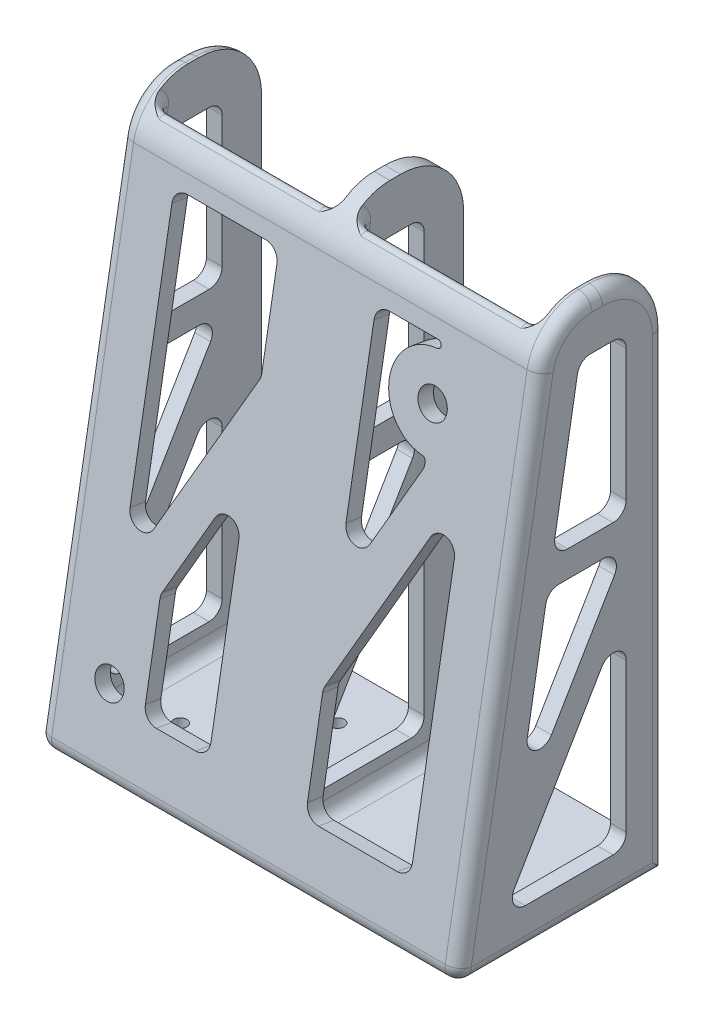
SolidWorks part; units mm, degrees
material "ABS"
ref_plane "X-Y Datum" through (0, 0, 0) normal (0, 0, 1) x (1, 0, 0)
ref_plane "X-Z Datum" through (0, 0, 0) normal (0, 1, 0) x (1, 0, 0)
ref_plane "Y-Z Datum" through (0, 0, 0) normal (1, 0, 0) x (0, 0, -1)
sketch "Sketch1" plane through (0, 0, 0) normal (1, 0, 0) x (0, 0, -1)
  line L0 (0, 0) -> (-50.8, 0)
  line L1 (-50.8, 0) -> (0, 294.1006)
  line L2 (0, 294.1006) -> (0, 0)
  dimension "D1" = 50.8
  dimension "D2" = 80.2
extrude "Boss-Extrude1" add sketch "Sketch1" along normal blind 101.6
fillet "Fillet1" [suppressed] radius 15.24
ref_plane "Plane2" through (50.8, 0, 0) normal (1, 0, 0) x (0, 0, -1)
sketch "Sketch3" plane through (50.8, 0, 0) normal (1, 0, 0) x (0, 0, -1)
  line L0 (-46.2755, 3.81) -> (-19.9514, 156.21)
  line L1 (-19.9514, 156.21) -> (0, 156.21)
  line L2 (0, 156.21) -> (0, 3.81)
  line L3 (0, 0) -> (0, 294.1006) construction
  line L4 (0, 3.81) -> (-46.2755, 3.81)
  line L5 (0, 294.1006) -> (-50.8, 0) construction
  line L6 (-46.2755, 3.81) -> (-46.2755, 0) construction
  line L7 (-50.8, 0) -> (0, 0) construction
  line L8 (-46.2755, 3.81) -> (-50.0299, 4.4585) construction
  dimension "D1" = 3.81
  dimension "D2" = 152.4
extrude "Cut-Extrude1" cut sketch "Sketch3" against normal offset from surface (45.085 mm away) 3.81 from offset 1.905 up to face at (0, 98.0335, 16.9333) offset against normal yes
extrude "Cut-Extrude2" cut sketch "Sketch3<3>" along normal offset from surface (45.085 mm away) 3.81 from offset 1.905 up to face at (101.6, 98.0335, 16.9333)
sketch "Sketch3<3>" plane through (50.8, 0, 0) normal (1, 0, 0) x (0, 0, -1) same geometry as "Sketch3"
sketch "Sketch4" plane through (101.6, 0, 0) normal (1, 0, 0) x (0, 0, -1)
  line L0 (0, 294.1006) -> (-28.5177, 129.0006)
  line L1 (0, 294.1006) -> (-50.8, 0) construction
  line L2 (-28.5177, 129.0006) -> (0, 129.0006)
  line L3 (0, 0) -> (0, 294.1006) construction
  line L4 (0, 129.0006) -> (0, 294.1006)
  dimension "D1" = 165.1
extrude "Cut-Extrude3" cut sketch "Sketch4" against normal through all both and the other way through all
fillet "Fillet2" radius 15.24 3 edges at (99.695, 129.0006, 0) (50.8, 129.0006, 0) (1.905, 129.0006, 0)
fillet "Fillet3" radius 12.7 1 edges at (50.8, 129.0006, 28.5177)
fillet "Fillet4" radius 1.27 2 edges at (75.2475, 126.7511, 25.0399) (26.3525, 126.7511, 25.0399)
fillet "Fillet5" radius 3.175 27 edges at (97.79, 124.3552, 26.4387) (48.895, 124.3552, 26.4387) (52.705, 124.3552, 26.4387) (3.81, 124.3552, 26.4387) (52.705, 3.81, 23.1377) (3.81, 3.81, 23.1377) (48.895, 3.81, 23.1377) (97.79, 3.81, 23.1377) (97.79, 63.3919, 35.9839) (48.895, 63.3919, 35.9839) (52.705, 63.3919, 35.9839) (3.81, 63.3919, 35.9839) (75.2475, 3.81, 46.2755) (26.3525, 3.81, 46.2755) (101.6, 56.8803, 0) (101.6, 124.5369, 4.4637) (101.6, 126.0151, 26.0037) (0, 56.8803, 0) (0, 124.5369, 4.4637) (0, 126.0151, 26.0037) (101.6, 59.2311, 40.569) (0, 59.2311, 40.569) (0, 0, 25.4) (50.8, 0, 50.8) (101.6, 0, 25.4) (101.6, 129.0006, 16.5317) (0, 129.0006, 16.5317)
sketch "Sketch5" plane through (0, 8.5205, 49.3283) normal (0, 0.1702, 0.9854) x (1, 0, 0)
  circle A1 centre (78.2877, 95.5297) radius 3.5
  circle A2 centre (14.478, 10.922) radius 3.5
  point P4 (0, 0)
  dimension "D3" = 7
  dimension "D6" = 7
  dimension "D1" = 14.478
  dimension "D2" = 10.922
  dimension "D4" = 63.8097
  dimension "D5" = 84.6077
extrude "Cut-Extrude4" cut sketch "Sketch5" against normal up to next
sketch "Sketch6" plane through (0, 3.81, 0) normal (0, 1, 0) x (1, 0, 0)
  line L0 (94.615, 0) -> (55.88, 0) construction
  line L1 (66.675, -12.7) -> (34.925, -12.7) construction
  line L2 (50.8, -24.12) -> (50.8, 24.12) construction
  line L3 (85.725, -31.75) -> (15.875, -31.75) construction
  circle A0 centre (66.675, -12.7) radius 1.5875
  circle A1 centre (34.925, -12.7) radius 1.5875
  circle A2 centre (85.725, -31.75) radius 1.5875
  circle A3 centre (15.875, -31.75) radius 1.5875
  point P6 (50.8, -12.7)
  point P13 (50.8, -31.75)
  dimension "D3" = 3.175
  dimension "D1" = 12.7
  dimension "D2" = 31.75
  dimension "D4" = 69.85
  dimension "D5" = 19.05
extrude "Cut-Extrude5" cut sketch "Sketch6" against normal up to next
sketch "Sketch7" plane through (0, 7.872, 45.5739) normal (0, -0.1702, -0.9854) x (-1, 0, 0)
  line L0 (-62.5475, 6.9294) -> (-87.9475, 6.9294)
  line L1 (-87.9475, 6.9294) -> (-87.9475, 83.1294)
  line L3 (-101.6, 57.3469) -> (0, 57.3469) construction
  line L4 (-50.8, 124.5242) -> (-50.8, -3.4804) construction
  line L5 (-52.705, 124.5242) -> (-48.895, 124.5242) construction
  line L9 (-55.88, -3.4804) -> (-94.615, -3.4804) construction
  line L10 (-101.6, -4.8762) -> (-101.6, 2.5883) construction
  line L11 (0, 111.5602) -> (0, 121.5716) construction
  line L13 (-94.615, 3.7544) -> (-55.88, 3.7544) construction
  line L14 (-75.2475, 6.9294) -> (-75.2475, 3.7544) construction
  line L15 (-62.5475, 6.9294) -> (-62.5475, 32.3294)
  line L16 (-62.5475, 32.3294) -> (-87.9475, 83.1294)
  line L17 (-39.0525, 107.7645) -> (-39.0525, 82.3645)
  line L18 (-39.0525, 82.3645) -> (-13.6525, 31.5645)
  line L19 (-13.6525, 107.7645) -> (-13.6525, 31.5645)
  line L20 (-39.0525, 107.7645) -> (-13.6525, 107.7645)
  line L21 (-87.9475, 83.1294) -> (-50.8, 57.3469) construction
  line L22 (-50.8, 57.3469) -> (-13.6525, 31.5645) construction
  line L24 (-62.5475, 83.1294) -> (-62.5475, 51.3794)
  line L25 (-62.5475, 51.3794) -> (-78.4225, 83.1294)
  line L27 (-39.0525, 32.3294) -> (-39.0525, 64.0794)
  line L28 (-39.0525, 64.0794) -> (-23.1775, 32.3294)
  line L29 (-78.4225, 83.1294) -> (-78.4225, 107.7645)
  line L30 (-62.5475, 107.7645) -> (-62.5475, 83.1294)
  line L31 (-78.4225, 107.7645) -> (-62.5475, 107.7645)
  line L33 (-23.1775, 32.3294) -> (-23.1775, 7.6943)
  line L34 (-23.1775, 7.6943) -> (-39.0525, 7.6943)
  line L35 (-39.0525, 7.6943) -> (-39.0525, 32.3294)
  point P16 (-50.8, 60.5219)
  dimension "D1" = 3.175
  dimension "D2" = 76.2
  dimension "D3" = 25.4
  dimension "D4" = 25.4
  dimension "D5" = 3.175
  dimension "D6" = 31.75
extrude "Cut-Extrude6" cut sketch "Sketch7" against normal through all both
sketch "Sketch8" plane through (0, 8.5205, 49.3283) normal (0, 0.1702, 0.9854) x (1, 0, 0)
  circle A0 centre (78.2877, 95.5297) radius 3.5
  arc A1 (78.4225, 92.0323) -> (78.4225, 99.0271) centre (78.2877, 95.5297) ccw construction
  circle A2 centre (78.2877, 95.5297) radius 10.5
  dimension "D1" = 7
extrude "Boss-Extrude2" add sketch "Sketch8" against normal up to surface (3.81 mm away) up to face at (73.6917, 96.7389, 30.2239)
fillet "Fillet6" radius 3.175 15 edges at (87.9475, 90.1126, 33.3016) (87.9475, 15.0245, 46.2716) (62.5475, 15.0245, 46.2716) (62.5475, 40.0539, 41.9483) (13.6525, 114.3882, 29.1085) (39.0525, 114.3882, 29.1085) (39.0525, 89.3588, 33.4318) (13.6525, 39.3001, 42.0785) (39.0525, 71.3406, 36.5441) (62.5475, 58.8259, 38.7058) (23.1775, 15.7783, 46.1414) (39.0525, 15.7783, 46.1414) (23.1775, 40.0539, 41.9483) (78.4225, 90.1126, 33.3016) (62.5475, 114.3882, 29.1085)
fillet "Fillet7" radius 0.889 3 edges at (78.4225, 91.986, 32.978) (78.4225, 112.6779, 29.4039) (78.4225, 114.3882, 29.1085)
sketch "Sketch9" plane through (50.8, 0, 0) normal (1, 0, 0) x (0, 0, -1)
  line L0 (-39.4887, 9.525) -> (-9.525, 60.325)
  line L1 (-9.525, 60.325) -> (-9.525, 9.525)
  line L2 (-9.525, 9.525) -> (-39.4887, 9.525)
  line L3 (-36.4357, 27.1999) -> (-28.5551, 72.8239)
  line L4 (-28.5551, 72.8239) -> (-9.525, 72.8239)
  line L5 (-9.525, 72.8239) -> (-36.4357, 27.1999)
  line L6 (-27.4582, 79.1739) -> (-20.8772, 117.2739)
  line L7 (-20.8772, 117.2739) -> (-9.525, 117.2739)
  line L8 (-9.525, 117.2739) -> (-9.525, 79.1739)
  line L9 (-9.525, 79.1739) -> (-27.4582, 79.1739)
  line L11 (-27.2093, 117.9219) -> (-47.0296, 3.175) construction
  line L12 (-39.4887, 9.525) -> (-36.4357, 27.1999) construction
  line L13 (-28.5551, 72.8239) -> (-27.4582, 79.1739) construction
  line L14 (-9.525, 60.325) -> (-9.525, 72.8239) construction
  line L15 (-9.525, 72.8239) -> (-9.525, 79.1739) construction
  line L16 (-36.4357, 27.1999) -> (-30.9663, 23.9738) construction
  line L17 (-9.525, 9.525) -> (-9.525, 3.175) construction
  line L18 (-47.0296, 3.175) -> (-3.175, 3.175) construction
  line L19 (-9.525, 9.525) -> (-3.175, 9.525) construction
  line L20 (-3.175, 3.175) -> (-3.175, 113.7606) construction
  line L21 (-39.4887, 9.525) -> (-45.746, 10.6058) construction
  dimension "D1" = 50.8
  dimension "D2" = 6.35
  dimension "D3" = 38.1
  dimension "D4" = 6.35
extrude "Cut-Extrude7" cut sketch "Sketch9" against normal up to next from surface starting at face at (101.6, 82.3159, 18.766)
extrude "Cut-Extrude8" cut sketch "Sketch9<2>" along normal up to next from surface starting at face at (0, 82.3159, 18.766)
sketch "Sketch9<2>" plane through (50.8, 0, 0) normal (1, 0, 0) x (0, 0, -1) same geometry as "Sketch9"
extrude "Cut-Extrude9" cut sketch "Sketch9<3>" against normal up to next and the other way up to next
sketch "Sketch9<3>" plane through (50.8, 0, 0) normal (1, 0, 0) x (0, 0, -1) same geometry as "Sketch9"
fillet "Fillet8" radius 3.175 30 edges at (1.905, 9.525, 9.525) (1.905, 9.525, 39.4887) (1.905, 60.325, 9.525) (1.905, 27.1999, 36.4357) (1.905, 72.8239, 28.5551) (1.905, 72.8239, 9.525) (1.905, 117.2739, 20.8772) (1.905, 117.2739, 9.525) (1.905, 79.1739, 9.525) (1.905, 79.1739, 27.4582) (50.8, 117.2739, 20.8772) (50.8, 117.2739, 9.525) (50.8, 9.525, 39.4887) (50.8, 79.1739, 27.4582) (50.8, 79.1739, 9.525) (50.8, 27.1999, 36.4357) (50.8, 72.8239, 28.5551) (50.8, 72.8239, 9.525) (50.8, 60.325, 9.525) (50.8, 9.525, 9.525) (99.695, 117.2739, 20.8772) (99.695, 117.2739, 9.525) (99.695, 79.1739, 27.4582) (99.695, 79.1739, 9.525) (99.695, 72.8239, 9.525) (99.695, 72.8239, 28.5551) (99.695, 27.1999, 36.4357) (99.695, 60.325, 9.525) (99.695, 9.525, 9.525) (99.695, 9.525, 39.4887)
